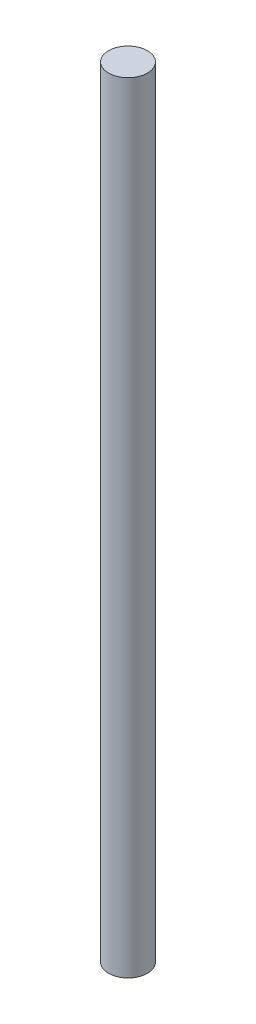
SolidWorks part; units mm, degrees
material "ALUMINUM 6061-T6"
ref_plane "Front Plane" through (0, 0, 0) normal (0, 0, 1) x (1, 0, 0)
ref_plane "Top Plane" through (0, 0, 0) normal (0, 1, 0) x (1, 0, 0)
ref_plane "Right Plane" through (0, 0, 0) normal (1, 0, 0) x (0, 0, -1)
sketch "Sketch1" plane through (0, 0, 0) normal (0, 1, 0) x (1, 0, 0)
  circle A0 centre (0, 0) radius 9.4996
extrude "Boss-Extrude1" add sketch "Sketch1" along normal mid plane 381
